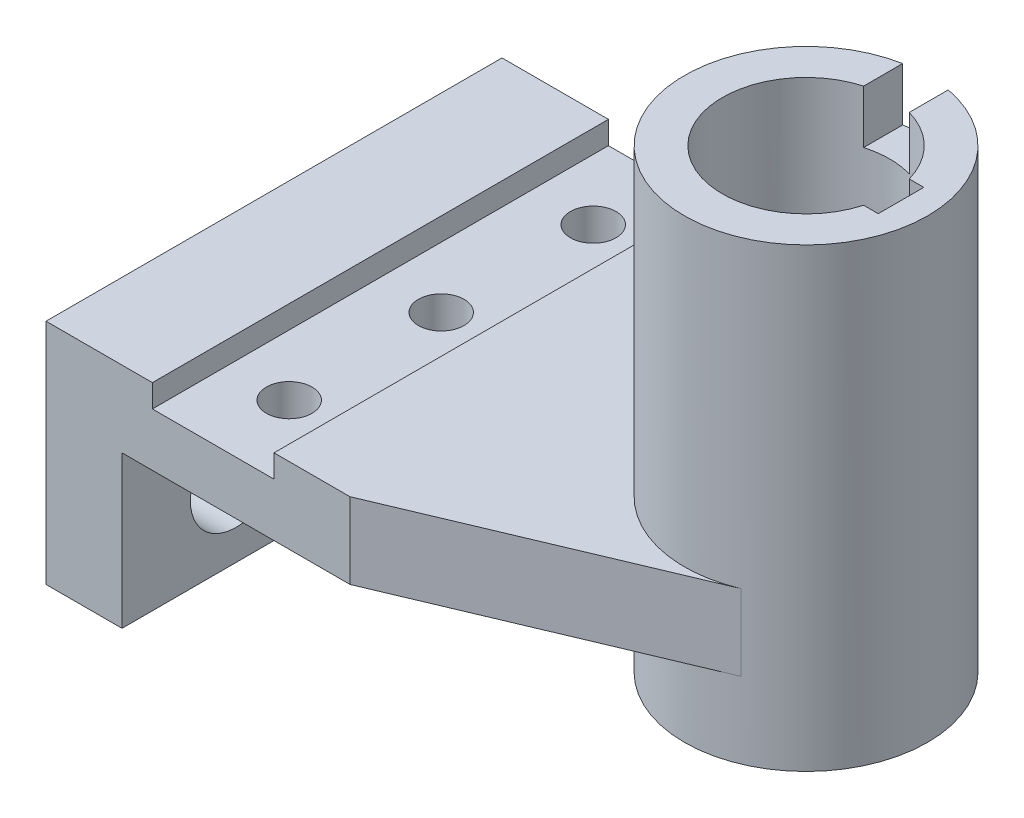
SolidWorks part; units mm, degrees
ref_plane "Front Plane" through (0, 0, 0) normal (0, 0, 1) x (1, 0, 0)
ref_plane "Top Plane" through (0, 0, 0) normal (0, 1, 0) x (1, 0, 0)
ref_plane "Right Plane" through (0, 0, 0) normal (1, 0, 0) x (0, 0, -1)
sketch "Sketch2" plane through (0, 0, 0) normal (0, 0, 1) x (1, 0, 0)
  line L0 (-32.6364, -18.7532) -> (-32.6364, 11.2468)
  line L1 (-32.6364, 11.2468) -> (-18.6364, 11.2468)
  line L2 (-18.6364, 11.2468) -> (-18.6364, 8.2468)
  line L3 (-18.6364, 8.2468) -> (-2.6364, 8.2468)
  line L4 (-2.6364, 8.2468) -> (-2.6364, 11.2468)
  line L5 (-2.6364, 11.2468) -> (37.3636, 11.2468)
  line L6 (37.3636, 11.2468) -> (37.3636, 1.2468)
  line L7 (37.3636, 1.2468) -> (-22.6364, 1.2468)
  line L8 (-22.6364, 1.2468) -> (-22.6364, -18.7532)
  line L9 (-22.6364, -18.7532) -> (-32.6364, -18.7532)
  dimension "D1" = 30
  dimension "D2" = 10
  dimension "D3" = 3
  dimension "D4" = 14
  dimension "D5" = 16
  dimension "D6" = 10
  dimension "D7" = 70
extrude "Boss-Extrude1" add sketch "Sketch2" along normal blind 60 contours L1 L2 L3 L4 L5 L6 L7 L8 L9 L0
sketch "Sketch3" plane through (-32.6364, 0, 0) normal (-1, 0, 0) x (0, 0, 1)
  line L0 (60, -18.7532) -> (60, 11.2468) construction
  line L1 (15, -8.7532) -> (45, -8.7532) construction
  line L2 (60, -18.7532) -> (0, -18.7532) construction
  circle A0 centre (45, -8.7532) radius 6
  circle A1 centre (15, -8.7532) radius 6
  dimension "D1" = 12
  dimension "D2" = 12
  dimension "D3" = 15
  dimension "D4" = 30
  dimension "D5" = 10
extrude "Cut-Extrude1" cut sketch "Sketch3" against normal up to surface (10 mm away) contours A1 | A0 region at (-32.6364, -8.7532, 15) up to face at (-22.6364, -8.7532, 30)
sketch "Sketch4" plane through (0, 8.2468, 0) normal (0, 1, 0) x (1, 0, 0)
  line L0 (-10.6364, -10) -> (-10.6364, -30) construction
  line L1 (-10.6364, -30) -> (-10.6364, -50) construction
  line L2 (-2.6364, -60) -> (-2.6364, 0) construction
  line L3 (-18.6364, -60) -> (-2.6364, -60) construction
  circle A0 centre (-10.6364, -30) radius 3
  circle A1 centre (-10.6364, -10) radius 3
  circle A2 centre (-10.6364, -50) radius 3
  dimension "D1" = 6
  dimension "D2" = 6
  dimension "D3" = 6
  dimension "D4" = 8
  dimension "D5" = 20
  dimension "D6" = 20
  dimension "D7" = 10
extrude "Cut-Extrude2" cut sketch "Sketch4" against normal up to surface (7 mm away) contours A2 | A1 | A0 region at (-10.6364, 8.2468, 50) up to face at (7.3636, 1.2468, 30)
sketch "Sketch5" plane through (0, 11.2468, 0) normal (0, 1, 0) x (1, 0, 0)
  line L0 (-2.6364, -60) -> (7.3636, -60)
  line L1 (-2.6364, -60) -> (37.3636, -60) construction
  line L2 (-32.6364, -60) -> (-32.6364, 0) construction
  line L3 (37.3636, -60) -> (37.3636, 0) construction
  line L4 (7.3636, -60) -> (43.5753, -44.745)
  line L5 (-2.6364, 0) -> (7.3636, 0)
  line L6 (7.3636, 0) -> (43.5753, -15.255)
  circle A0 centre (37.3636, -30) radius 16
  circle A1 centre (37.3636, -30) radius 11
  line M3 (37.3636, 0) -> (-2.6364, 0)
  line M5 (-2.6364, -60) -> (37.3636, -60)
  line M6 (37.3636, -60) -> (37.3636, 0)
  dimension "D2" = 32
  dimension "D3" = 22
  dimension "D1" = 40
extrude "Boss-Extrude2" add sketch "Sketch5" along normal blind 40 and the other way offset from surface 10 contours A1 A0 M6 | A1 A0 M6 region at (40.4614, 11.2468, 45.3324) region at (21.7214, 11.2468, 30) other way up to face at (-27.6364, -18.7532, 30)
extrude "Cut-Extrude3" cut sketch "Sketch5<4>" against normal blind 40 and the other way through all contours L6 M3 M6 | L4 M5 M6 region at (27.3636, 11.2468, 4.2127) region at (27.3636, 11.2468, 55.7873)
sketch "Sketch5<4>" plane through (0, 11.2468, 0) normal (0, 1, 0) x (1, 0, 0) same geometry as "Sketch5"
sketch "Sketch7" plane through (0, 11.2468, 0) normal (0, 1, 0) x (1, 0, 0)
  line L0 (37.3636, -12.6382) -> (43.5753, -15.255)
  line L1 (43.5753, -15.255) -> (43.5753, -44.745)
  line L2 (43.5753, -44.745) -> (37.3636, -47.3618)
  line L3 (37.3636, -47.3618) -> (37.3636, -12.6382)
extrude "Boss-Extrude3" add sketch "Sketch7" against normal up to surface (10 mm away) contours L1 L2 L3 L0 up to face at (-7.6364, 1.2468, 50)
sketch "Sketch9" plane through (0, 51.2468, 0) normal (0, 1, 0) x (1, 0, 0)
  line L0 (37.3636, -30) -> (49.8636, -30) construction
  line L2 (49.8636, -27) -> (49.8636, -33)
  line L3 (49.8636, -33) -> (47.385, -33)
  line L4 (47.385, -33) -> (47.385, -27)
  line L5 (47.385, -27) -> (49.8636, -27)
  line L6 (37.3636, -30) -> (37.3636, -5.0203) construction
  line L8 (34.3636, -5.0203) -> (40.3636, -5.0203)
  line L9 (34.3636, -5.0203) -> (34.3636, -30)
  line L10 (34.3636, -30) -> (40.3636, -30)
  line L11 (40.3636, -5.0203) -> (40.3636, -30)
  line L12 (34.3636, -5.0203) -> (40.3636, -30) construction
  line L13 (34.3636, -30) -> (40.3636, -5.0203) construction
  circle A0 centre (37.3636, -30) radius 11
  point P9 (37.3636, -17.5102)
  dimension "D1" = 22
  dimension "D2" = 12.5
  dimension "D3" = 6
  dimension "D4" = 3
  dimension "D5" = 6
extrude "Cut-Extrude4" cut sketch "Sketch9" against normal up to surface (60 mm away) contours A0 up to face at (53.3636, -8.7532, 30)
extrude "Cut-Extrude5" cut sketch "Sketch9<3>" against normal up to surface (60 mm away) contours L2 L3 L4 L5 up to face at (53.3636, -8.7532, 30)
sketch "Sketch9<3>" plane through (0, 51.2468, 0) normal (0, 1, 0) x (1, 0, 0) same geometry as "Sketch9"
extrude "Cut-Extrude6" cut sketch "Sketch9<4>" against normal blind 7 contours L8 L11 L10 L9
sketch "Sketch9<4>" plane through (0, 51.2468, 0) normal (0, 1, 0) x (1, 0, 0) same geometry as "Sketch9"
